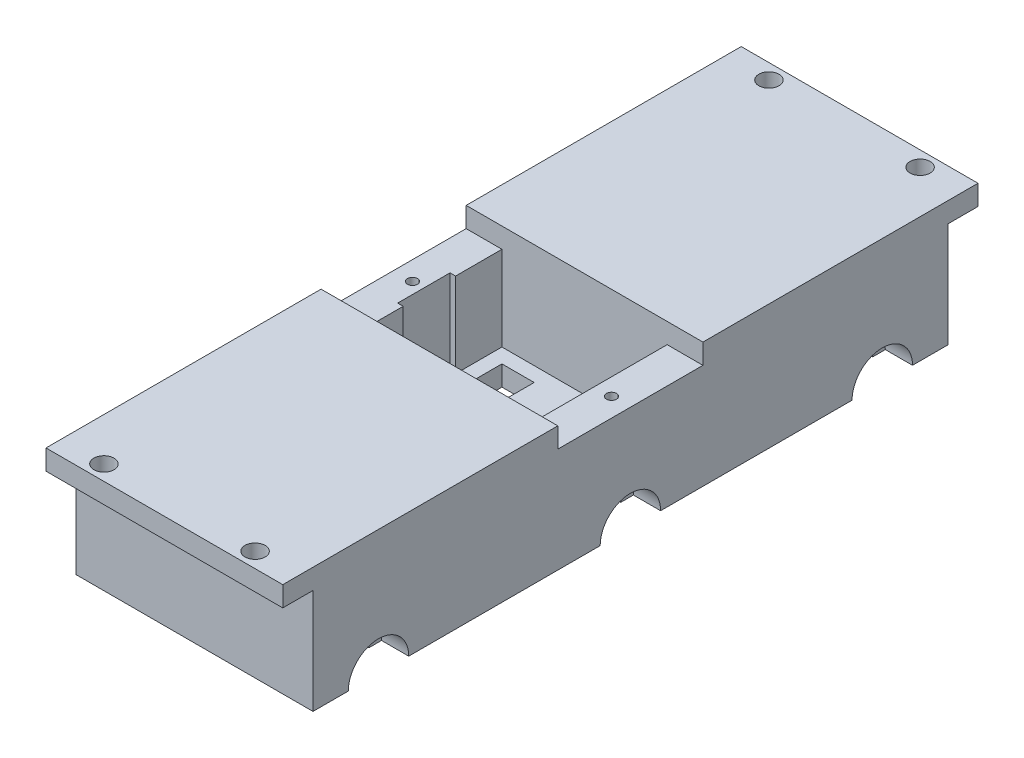
SolidWorks part; units mm, degrees
other "标注1"
sketch "草图3" plane through (-22.25, 4, -10) normal (-0.231, 0.6469, -0.7268) x (-0.9696, -0.2151, 0.1167)
ref_plane "前视基准面" through (0, 0, 0) normal (0, 0, 1) x (1, 0, 0)
ref_plane "上视基准面" through (0, 0, 0) normal (0, 1, 0) x (1, 0, 0)
ref_plane "右视基准面" through (0, 0, 0) normal (1, 0, 0) x (0, 0, -1)
other "Configuration Table"
sketch "草图4" plane through (0, 0, 0) normal (0, 1, 0) x (1, 0, 0)
  line L1 (-23, -53.75) -> (23, -53.75)
  line L2 (-23, -53.75) -> (-23, 53.75)
  line L3 (-23, 53.75) -> (23, 53.75)
  line L4 (23, -53.75) -> (23, 53.75)
  line L5 (-23, -53.75) -> (23, 53.75) construction
  line L6 (-23, 53.75) -> (23, -53.75) construction
  point P0 (0, 0)
  dimension "D1" = 107.5
  dimension "D2" = 46
extrude "凸台-拉伸1" add sketch "草图4" along normal blind 3
sketch "草图5" plane through (0, 0, 0) normal (0, -1, 0) x (1, 0, 0)
  line L0 (-11.75, 31.5) -> (11.75, -31.5) construction
  line L1 (-11.75, 31.5) -> (11.75, 31.5)
  line L2 (-11.75, 31.5) -> (-11.75, -31.5)
  line L3 (-11.75, -31.5) -> (11.75, -31.5)
  line L4 (11.75, 31.5) -> (11.75, -31.5)
  dimension "D1" = 63
  dimension "D2" = 23.5
extrude "凸台-拉伸2" add sketch "草图5" along normal blind 12.4
sketch "草图6" plane through (-11.75, 0, 0) normal (-1, 0, 0) x (0, 0, 1)
  line L0 (31.5, -12.4) -> (-31.5, -12.4) construction
  line L1 (-25, -12.4) -> (25, -12.4)
  circle A0 centre (0, -12.4) radius 1.75
  circle A1 centre (0, -12.4) radius 3
  circle A2 centre (25, -12.4) radius 1.75
  circle A3 centre (25, -12.4) radius 3
  circle A4 centre (-25, -12.4) radius 1.75
  circle A5 centre (-25, -12.4) radius 3
  dimension "D1" = 3.5
  dimension "D2" = 6
  dimension "D5" = 50
extrude "切除-拉伸1" cut sketch "草图6" against normal through all contours A4 | A0 | A2
extrude "切除-拉伸2" cut sketch "草图6<3>" against normal blind 2.7 contours A1
sketch "草图6<3>" plane through (-11.75, 0, 0) normal (-1, 0, 0) x (0, 0, 1) same geometry as "草图6"
extrude "切除-拉伸3" cut sketch "草图6<4>" along normal blind 2.7 from surface contours A1 starting at face at (11.75, -9.395, 0)
sketch "草图6<4>" plane through (-11.75, 0, 0) normal (-1, 0, 0) x (0, 0, 1) same geometry as "草图6"
extrude "切除-拉伸4" cut sketch "草图6<5>" against normal blind 2.7 contours A3 | A5
sketch "草图6<5>" plane through (-11.75, 0, 0) normal (-1, 0, 0) x (0, 0, 1) same geometry as "草图6"
extrude "切除-拉伸5" cut sketch "草图6<6>" along normal blind 2.7 from surface contours A3 | A5 starting at face at (11.75, -9.27, 0)
sketch "草图6<6>" plane through (-11.75, 0, 0) normal (-1, 0, 0) x (0, 0, 1) same geometry as "草图6"
sketch "草图7" plane through (0, -12.4, 0) normal (0, -1, 0) x (-1, 0, 0)
  line L0 (9.2499, -6) -> (9.2499, 6) construction
  line L1 (-9.2499, -20) -> (-9.2499, 20) construction
  line L2 (9.2499, 0) -> (-9.2499, 0) construction
  circle A0 centre (9.2499, -20) radius 0.7
  circle A1 centre (-9.2499, -20) radius 0.7
  circle A2 centre (-9.2499, -6) radius 0.7
  circle A3 centre (9.2499, -6) radius 0.7
  circle A4 centre (9.2499, 6) radius 0.7
  circle A5 centre (-9.2499, 6) radius 0.7
  circle A6 centre (-9.2499, 20) radius 0.7
  circle A7 centre (9.2499, 20) radius 0.7
  dimension "D1" = 1.4
  dimension "D2" = 18.4999
  dimension "D3" = 12
  dimension "D4" = 40
extrude "切除-拉伸6" cut sketch "草图7" against normal blind 2
sketch "草图8" plane through (0, -12.4, 0) normal (0, -1, 0) x (1, 0, 0)
  line L1 (-8.2, 7.2) -> (8.2, 7.2)
  line L2 (-8.2, 7.2) -> (-8.2, -7.2)
  line L3 (-8.2, -7.2) -> (8.2, -7.2)
  line L4 (8.2, 7.2) -> (8.2, -7.2)
  line L8 (-8.2, 7.2) -> (-11.75, 7.2) construction
  line L9 (-11.75, -3) -> (-11.75, -22) construction
  line L10 (11.75, 7.2) -> (8.2, 7.2) construction
  line L11 (11.75, -22) -> (11.75, -3) construction
  line L12 (8.2, 31.5) -> (8.2, 7.2) construction
  line L13 (11.75, 31.5) -> (-11.75, 31.5) construction
  line L14 (8.2, -31.5) -> (8.2, -7.2) construction
  line L15 (-11.75, -31.5) -> (11.75, -31.5) construction
  dimension "D1" = 14.4
  dimension "D2" = 16.4
extrude "切除-拉伸7" cut sketch "草图8" against normal through all from offset 2 offset against normal yes
sketch "草图9" plane through (0, 0, 0) normal (0, -1, 0) x (1, 0, 0)
  line L0 (-23, 53.75) -> (23, 53.75) construction
  line L1 (-23, 53.75) -> (23, 53.75)
  line L2 (-23, 53.75) -> (-23, 45.75)
  line L3 (-23, 45.75) -> (23, 45.75)
  line L4 (23, 53.75) -> (23, 45.75)
  line L5 (23, 53.75) -> (23, -53.75) construction
  line L6 (23, -53.75) -> (-23, -53.75) construction
  line L7 (-23, -53.75) -> (23, -53.75)
  line L8 (-23, -53.75) -> (-23, -45.75)
  line L9 (-23, -45.75) -> (23, -45.75)
  line L10 (23, -53.75) -> (23, -45.75)
  line L11 (-23, -53.75) -> (-23, 53.75) construction
  line L12 (-23, 41.9103) -> (-20, 41.9103) construction
  line L13 (-20, 45.75) -> (-23, 45.75)
  line L14 (-20, 45.75) -> (-20, -45.75)
  line L15 (-20, -45.75) -> (-23, -45.75)
  line L16 (-23, 45.75) -> (-23, -45.75)
  line L17 (23, -45.75) -> (20, -45.75)
  line L18 (23, -45.75) -> (23, 45.75)
  line L19 (23, 45.75) -> (20, 45.75)
  line L20 (20, -45.75) -> (20, 45.75)
  line L22 (20, 41.9103) -> (23, 41.9103) construction
  line M17 (23, -53.75) -> (23, 53.75)
  line M18 (23, 53.75) -> (-23, 53.75)
  line M19 (-23, 53.75) -> (-23, -53.75)
  line M20 (-23, -53.75) -> (23, -53.75)
  dimension "D1" = 8
  dimension "D2" = 3
extrude "凸台-拉伸3" add sketch "草图9" along normal blind 10 contours L3 M19 M17 M18 | L9 M19 M20 M17 region at (0, 0, 49.75) region at (0, 0, -49.75)
extrude "凸台-拉伸4" add sketch "草图9<3>" along normal blind 3 contours L14 L3 L9 M19 | L20 L9 L3 M17 region at (-21.5, 0, 0) region at (21.5, 0, 0)
sketch "草图9<3>" plane through (0, 0, 0) normal (0, -1, 0) x (1, 0, 0) same geometry as "草图9"
sketch "草图10" plane through (0, 0, 53.75) normal (0, 0, 1) x (1, 0, 0)
  line L1 (-7.5, 0) -> (7.5, 0) construction
  circle A0 centre (-7.5, 0) radius 0.6
  circle A1 centre (7.5, 0) radius 0.6
  dimension "D2" = 1.2
  dimension "D1" = 15
extrude "切除-拉伸8" cut sketch "草图10" against normal blind 2
sketch "草图11" plane through (0, 3, 0) normal (0, 1, 0) x (1, 0, 0)
  line L0 (-8.2, 7.2) -> (8.2, 7.2) construction
  line L1 (-13.2, 7.2) -> (13.2, 7.2)
  line L2 (-13.2, 7.2) -> (-13.2, -7.2)
  line L3 (-13.2, -7.2) -> (13.2, -7.2)
  line L4 (13.2, 7.2) -> (13.2, -7.2)
  line L5 (8.2, -7.2) -> (-8.2, -7.2) construction
  line L6 (-13.2, 0) -> (13.2, 0) construction
  line L7 (-8.2, -7.2) -> (-8.2, 7.2) construction
  dimension "D1" = 5
extrude "切除-拉伸9" cut sketch "草图11" against normal blind 5
sketch "草图12" plane through (0, -2, 0) normal (0, 1, 0) x (1, 0, 0)
  line L0 (-9.875, 0) -> (9.875, 0) construction
  circle A0 centre (-9.875, 0) radius 0.5
  circle A1 centre (9.875, 0) radius 0.5
  dimension "D1" = 1
  dimension "D2" = 19.75
extrude "切除-拉伸10" cut sketch "草图12" against normal blind 2
sketch "草图13" plane through (0, -12.4, 0) normal (0, -1, 0) x (1, 0, 0)
  line L0 (-8.75, 2.6) -> (-6.75, 2.6)
  line L1 (-6.75, 2.6) -> (-6.75, 5.75)
  line L2 (-6.75, 5.75) -> (-3.55, 5.75)
  line L3 (-3.55, 5.75) -> (-3.55, -5.75)
  line L4 (-3.55, -5.75) -> (-6.75, -5.75)
  line L5 (-6.75, -5.75) -> (-6.75, -2.6)
  line L6 (-6.75, -2.6) -> (-8.75, -2.6)
  line L7 (-8.75, -2.6) -> (-8.75, 2.6)
  line L8 (-11.75, 22) -> (-11.75, 3) construction
  line L9 (-9.05, 0) -> (-8.75, 0) construction
  line L10 (-9.05, 1.75) -> (-9.05, -1.75) construction
  dimension "D1" = 3
  dimension "D2" = 5.2
  dimension "D3" = 11.5
  dimension "D4" = 2
  dimension "D5" = 3.2
extrude "切除-拉伸11" cut sketch "草图13" against normal through all
sketch "草图14" plane through (0, 0, 31.5) normal (0, 0, 1) x (1, 0, 0)
  line L5 (23, 3) -> (23, -10) construction
  line L6 (-23, 3) -> (23, 3)
  line L7 (-23, 3) -> (-23, 0)
  line L8 (-23, 0) -> (23, 0)
  line L9 (23, 3) -> (23, 0)
  dimension "D1" = 3
extrude "切除-拉伸12" cut sketch "草图14" against normal through all both and the other way through all
sketch "草图15" plane through (0, -12.4, 0) normal (0, -1, 0) x (1, 0, 0)
  line L0 (-11.75, 22) -> (-11.75, 3) construction
  line L1 (-11.75, 31.5) -> (11.75, 31.5)
  line L2 (-11.75, 31.5) -> (-11.75, -31.5)
  line L3 (-11.75, -31.5) -> (11.75, -31.5)
  line L4 (11.75, 31.5) -> (11.75, -31.5)
  line L5 (11.75, 31.5) -> (-11.75, 31.5) construction
  line L6 (-11.75, -31.5) -> (11.75, -31.5) construction
  line L7 (11.75, -22) -> (11.75, -3) construction
extrude "切除-拉伸15" cut sketch "草图15" against normal through all flip side to cut
sketch "草图16" plane through (0, 0, 0) normal (0, 1, 0) x (1, 0, 0)
  line L0 (11.75, 31.5) -> (11.75, 7.2) construction
  line L1 (-11.75, 31.5) -> (11.75, 31.5)
  line L2 (-11.75, 31.5) -> (-11.75, 34.5)
  line L3 (-11.75, 34.5) -> (11.75, 34.5)
  line L4 (11.75, 31.5) -> (11.75, 34.5)
  line L5 (-11.75, 33) -> (-7.5, 33) construction
  line L6 (-7.5, 33) -> (7.5, 33) construction
  line L7 (7.5, 33) -> (11.75, 33) construction
  line L8 (-11.75, -33) -> (-7.5, -33) construction
  line L9 (-11.75, -31.5) -> (11.75, -31.5)
  line L10 (-11.75, -31.5) -> (-11.75, -34.5)
  line L11 (-11.75, -34.5) -> (11.75, -34.5)
  line L12 (11.75, -31.5) -> (11.75, -34.5)
  line L13 (-7.5, -33) -> (7.5, -33) construction
  line L14 (7.5, -33) -> (11.75, -33) construction
  line L15 (11.75, -7.2) -> (11.75, -31.5) construction
  circle A0 centre (-7.5, 33) radius 1
  circle A1 centre (7.5, 33) radius 1
  circle A2 centre (-7.5, -33) radius 1
  circle A3 centre (7.5, -33) radius 1
  dimension "D2" = 2
  dimension "D1" = 3
  dimension "D3" = 15
extrude "凸台-拉伸5" add sketch "草图16" against normal blind 2
sketch "草图17" plane through (9.05, 0, 0) normal (1, 0, 0) x (0, 0, -1)
  circle A0 centre (0, -12.4) radius 5.75
  arc A1 (3, -12.4) -> (-3, -12.4) centre (0, -12.4) ccw construction
  dimension "D1" = 11.5
extrude "切除-拉伸16" cut sketch "草图17" against normal blind 3.4 from offset 1 offset against normal yes
sketch "草图18" plane through (4.65, 0, 0) normal (1, 0, 0) x (0, 0, -1)
  line L0 (-3, -12.4) -> (-22, -12.4) construction
  line L1 (22, -12.4) -> (3, -12.4) construction
  circle A0 centre (-12.5, -12.4) radius 8.25
  circle A1 centre (12.5, -12.4) radius 8.25
  dimension "D1" = 16.5
extrude "切除-拉伸17" cut sketch "草图18" along normal blind 2 from offset 0.4
sketch "草图19" plane through (5.05, 0, 0) normal (1, 0, 0) x (0, 0, -1)
  line L0 (-3, -12.4) -> (-22, -12.4) construction
  line L1 (22, -12.4) -> (3, -12.4) construction
  circle A0 centre (-12.5, -12.4) radius 3.25
  circle A1 centre (12.5, -12.4) radius 3.25
  dimension "D1" = 6.5
extrude "切除-拉伸18" cut sketch "草图19" against normal blind 4
sketch "草图20" plane through (7.05, 0, 0) normal (-1, 0, 0) x (0, 0, 1)
  circle A0 centre (-25, -12.4) radius 5.75
  arc A1 (-23.25, -12.4) -> (-26.75, -12.4) centre (-25, -12.4) ccw construction
  circle A2 centre (25, -12.4) radius 5.75
  arc A3 (28, -12.4) -> (22, -12.4) centre (25, -12.4) ccw construction
  dimension "D1" = 11.5
extrude "切除-拉伸19" cut sketch "草图20" along normal blind 3.4
sketch "草图21" plane through (11.75, 0, 0) normal (1, 0, 0) x (0, 0, -1)
  line L0 (-3, -12.4) -> (-22, -12.4) construction
  line L1 (22, -12.4) -> (3, -12.4) construction
  circle A0 centre (-12.5, -12.4) radius 1
  circle A1 centre (12.5, -12.4) radius 1
  arc A2 (15.75, -12.4) -> (9.25, -12.4) centre (12.5, -12.4) ccw construction
  arc A3 (-9.25, -12.4) -> (-15.75, -12.4) centre (-12.5, -12.4) ccw construction
  dimension "D1" = 2
extrude "切除-拉伸20" cut sketch "草图21" along normal blind 3 from surface starting at face at (7.05, -9.5935, 16.064)
extrude "切除-拉伸21" cut sketch "草图21<2>" against normal blind 3 from surface starting at face at (1.05, -10.775, 12.5)
sketch "草图21<2>" plane through (11.75, 0, 0) normal (1, 0, 0) x (0, 0, -1) same geometry as "草图21"
